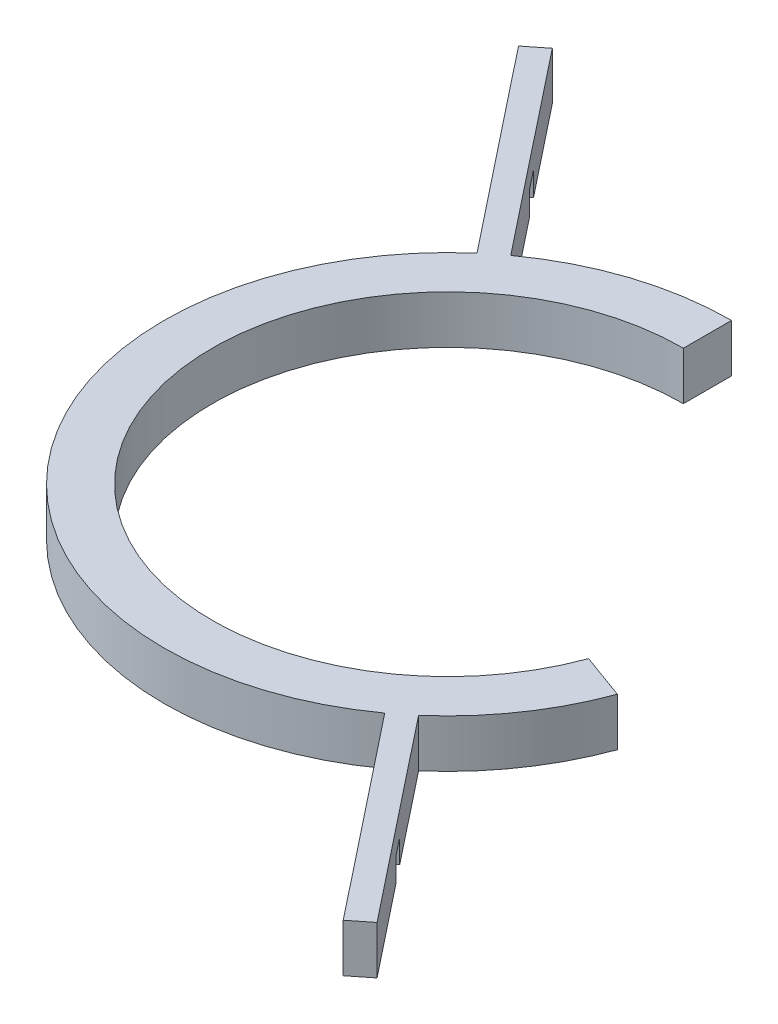
SolidWorks part; units mm, degrees
ref_plane "Front Plane" through (0, 0, 0) normal (0, 0, 1) x (1, 0, 0)
ref_plane "Top Plane" through (0, 0, 0) normal (0, 1, 0) x (1, 0, 0)
ref_plane "Right Plane" through (0, 0, 0) normal (1, 0, 0) x (0, 0, -1)
sketch "Sketch1" plane through (0, 0, 0) normal (0, 1, 0) x (1, 0, 0)
  line L0 (0, 4.9) -> (0, 5.9)
  line L1 (4.6045, -1.6759) -> (5.5442, -2.0179)
  line L2 (-6.2111, 7.8372) -> (6.2111, -7.8372)
  line L3 (3.4653, -4.7751) -> (6.7638, -8.9371)
  line L4 (3.8572, -4.4645) -> (7.1557, -8.6266)
  line L5 (6.7638, -8.9371) -> (7.1557, -8.6266)
  line L6 (-3.8572, 4.4645) -> (-7.1557, 8.6266)
  line L7 (-3.4653, 4.7751) -> (-6.7638, 8.9371)
  line L8 (-6.7638, 8.9371) -> (-7.1557, 8.6266)
  line L9 (-5.4506, -4.3197) -> (5.4506, 4.3197)
  line L10 (5.1146, -6.8561) -> (5.5064, -6.5456) construction
  circle A0 centre (0, 0) radius 5.9
  circle A1 centre (0, 0) radius 4.9
  point P11 (0, 0)
  point P13 (-5.3492, 0.0934)
  point P15 (-4.3493, 0.0759)
  point P18 (3.4653, -4.7751)
  point P19 (0, 0)
  point P23 (0, 0)
  point P26 (-0.0247, 0.0404)
  point P27 (0, 0)
  point P30 (0, 0)
  point P31 (0, 0)
  point P32 (3.321, -4.5983)
  point P33 (3.4653, -4.7751)
  dimension "D1" = 1
  dimension "D3" = 11.8
  dimension "D6" = 8.55
  dimension "D2" = 110
  dimension "D4" = 2
  dimension "D5" = 0.5
extrude "Boss-Extrude2" add sketch "Sketch1" along normal blind 1 contours A1 L9 A0 L2 | A1 L2 A0 L9 | A0 L7 L8 L6 | A1 L0 A0 L2 | A1 L2 A0 L1 | L3 L10 L2 A0 | L10 L3 L5 L4 | L2 L10 L4 A0 region at (-1.7477, 0, -5.0191) region at (-4.9546, 0, -0.5735) region at (-3.6008, 0, -4.7468) region at (-0.5735, 0, 4.9546) region at (4.3367, 0, 3.1279) region at (4.585, 0, 5.584) region at (4.389, 0, 5.7394) region at (5.428, 0, 6.6478)
sketch "Sketch2" plane through (-0.1959, 0, 0.1553) normal (-0.7837, 0, 0.6211) x (0.6211, 0, 0.7837)
  line L0 (8.55, 1) -> (8.55, 0) construction
  line L1 (5.8947, 1) -> (11.2053, 1) construction
  line L2 (5.8947, 0) -> (11.2053, 0) construction
  line L3 (8.3, 0) -> (8.3, 0.5)
  line L4 (8.3, 0.5) -> (8.8, 0.5)
  line L5 (8.8, 0.5) -> (8.8, 0)
  line L6 (8.3, 0) -> (8.8, 0)
  line L8 (0, 0) -> (0, 4.985) construction
  line L11 (-8.3, 0) -> (-8.3, 0.5)
  line L12 (-8.3, 0.5) -> (-8.8, 0.5)
  line L13 (-8.8, 0.5) -> (-8.8, 0)
  line L14 (-8.3, 0) -> (-8.8, 0)
  line L15 (-8.55, 0) -> (-8.55, 1)
  line L16 (-5.8947, 1) -> (-11.2053, 1) construction
  point P17 (0, 0)
  point P23 (-8.55, 0.5)
  line M5 (5.8947, 0) -> (11.2053, 0)
  dimension "D1" = 0.5
  dimension "D3" = 0.5
extrude "Cut-Extrude2" cut sketch "Sketch2" against normal blind 1 contours L14 L11 L12 L13 | L5 L4 L3 M5 | L11 L12 L13 L14 region at (5.1146, 0.25, 6.8561) region at (-5.5841, 0.25, -6.6435)
